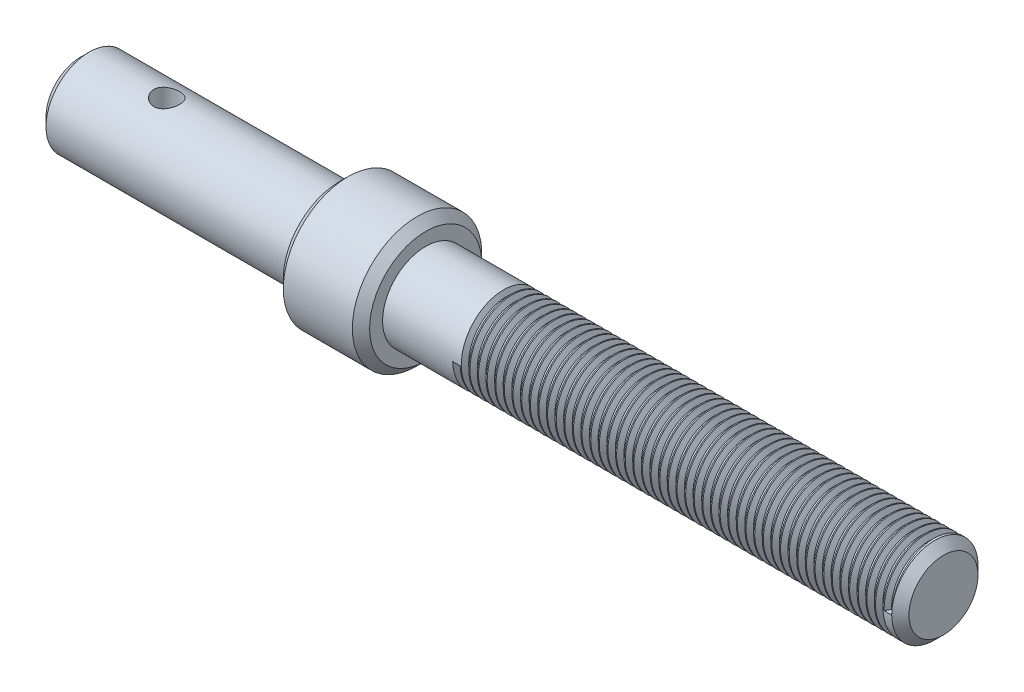
SolidWorks part; units mm, degrees
ref_plane "Front Plane" through (0, 0, 0) normal (0, 0, 1) x (1, 0, 0)
ref_plane "Top Plane" through (0, 0, 0) normal (0, 1, 0) x (1, 0, 0)
ref_plane "Right Plane" through (0, 0, 0) normal (1, 0, 0) x (0, 0, -1)
sketch "Sketch1" plane through (0, 0, 0) normal (0, 0, 1) x (1, 0, 0)
  line L0 (0, 0) -> (100, 0) construction
  line L1 (30, 7.5) -> (30, 5)
  line L2 (30, 7.5) -> (40, 7.5)
  line L3 (40, 7.5) -> (40, 5)
  line L4 (40, 5) -> (100, 5)
  line L5 (100, 5) -> (100, 0)
  line L6 (0, 0) -> (100, 0)
  line L7 (30, 5) -> (0, 5)
  line L8 (0, 5) -> (0, 0)
  dimension "D1" = 10
  dimension "D2" = 15
  dimension "D3" = 60
  dimension "D4" = 30
  dimension "D5" = 10
revolve "Corpo" add sketch "Sketch1" angle 360 about L0
fillet "Chanfro 1x45°" radius 1 4 edges at (100, 0, 5) (40, 0, 7.5) (30, 0, 7.5) (0, 0, 5) profile chamfer
thread "Rosca M10x50" pitch 1 method cut profile "Thread Profile2" start angle 0, offset 0, length 50, pitch 1, diameter 10
ref_plane "Plane2" through (99, 0, 5) normal (0, -1, 0) x (0, 0, 1)
sketch "Thread Profile2" plane through (99, 0, 5) normal (0, -1, 0) x (0, 0, 1)
  line L0 (0, 0) -> (0, 1) construction
  line L11 (0, 0) -> (0, 0.875)
  line L12 (0, 0.875) -> (-0.5413, 0.5625)
  line L13 (-0.5413, 0.5625) -> (-0.5413, 0.3125)
  line L15 (-0.5413, 0.3125) -> (0, 0)
  line L17 (-0.5413, 0.4375) -> (0, 0.4375) construction
  point P2 (0, 0)
  dimension "Pitch" = 1
  dimension "Profile_Angle" = 60
  dimension "Profile_Land" = 0.25
  dimension "Profile_Height" = 0.5413
ref_plane "Plano de Referência" through (0, 7.5, 0) normal (0, 1, 0) x (1, 0, 0)
sketch "Posição do Furo" plane through (0, 7.5, 0) normal (0, 1, 0) x (1, 0, 0)
  line L0 (10, 5) -> (10, -5) construction
  line L1 (0, 4) -> (0, -4) construction
  line L3 (0, 0) -> (30, 0) construction
  line L5 (30, 5) -> (30, -5) construction
  line L6 (1, -5) -> (30, -5) construction
  line L7 (30, 5) -> (1, 5) construction
  circle A0 centre (10, 0) radius 1.5
  dimension "D1" = 3
  dimension "D2" = 10
extrude "Furo Ø3 Passante" cut sketch "Posição do Furo" against normal through all
